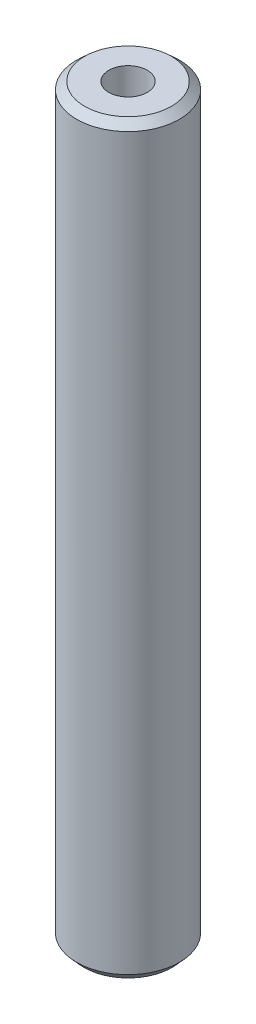
SolidWorks part; units mm, degrees
ref_plane "Front Plane" through (0, 0, 0) normal (0, 0, 1) x (1, 0, 0)
ref_plane "Top Plane" through (0, 0, 0) normal (0, 1, 0) x (1, 0, 0)
ref_plane "Right Plane" through (0, 0, 0) normal (1, 0, 0) x (0, 0, -1)
sketch "Sketch1" plane through (0, 0, 0) normal (0, 1, 0) x (1, 0, 0)
  circle A0 centre (0, 0) radius 20
  dimension "SHAFT_OD" = 40
extrude "Boss-Extrude1" add sketch "Sketch1" along normal blind 290.2005
sketch "Sketch2" plane through (0, 0, 0) normal (0, 1, 0) x (1, 0, 0)
  circle A0 centre (0, 0) radius 7.4857
  dimension "BORE_D" = 14.9714
extrude "Cut-Extrude1" cut sketch "Sketch2" along normal through all
chamfer "Chamfer1" distance 2.8221 angle 47.921 2 edges at (0, 290.2005, 20) (0, 0, 20) first distance on face at (0, 290.2005, 20) first distance on face at (0, 0, 7.4857)
